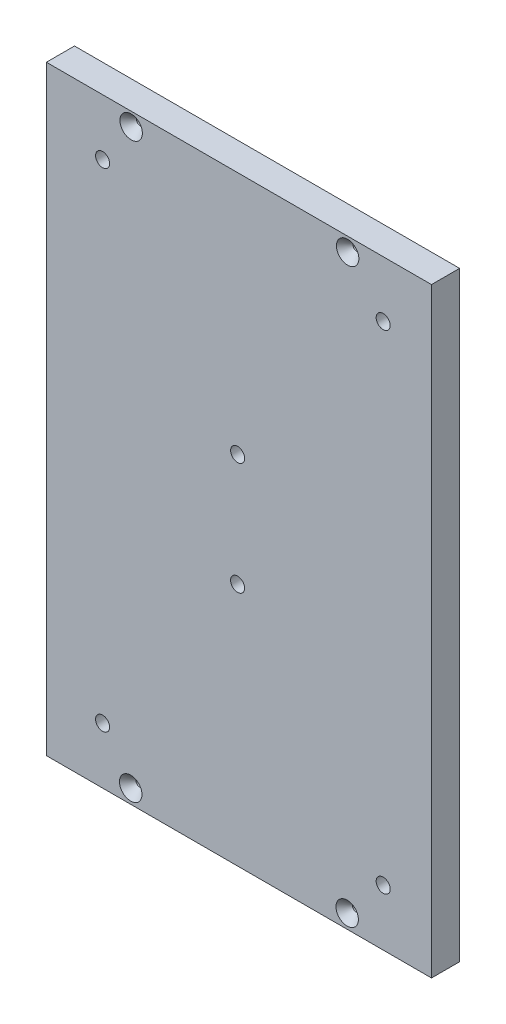
SolidWorks part; units mm, degrees
material "Beech"
ref_plane "Front Plane" through (0, 0, 0) normal (0, 0, 1) x (1, 0, 0)
ref_plane "Top Plane" through (0, 0, 0) normal (0, 1, 0) x (1, 0, 0)
ref_plane "Right Plane" through (0, 0, 0) normal (1, 0, 0) x (0, 0, -1)
sketch "Sketch1" plane through (0, 0, 0) normal (0, 0, 1) x (1, 0, 0)
  line L2 (125.2425, 0) -> (299.2638, 0)
  line L3 (125.2425, 0) -> (125.2425, 271.3655)
  line L4 (125.2425, 135.6828) -> (299.2638, 135.6828) construction
  line L5 (299.2638, 0) -> (299.2638, 271.3655)
  line L8 (125.2425, 271.3655) -> (299.2638, 271.3655)
  line L9 (299.2638, 0) -> (299.2638, 271.3655) construction
  point P15 (299.2638, 135.6828)
  point P16 (299.2638, 135.6828)
extrude "Boss-Extrude1" add sketch "Sketch1" along normal blind 12.7
hole_wizard "1/4 (0.25) Diameter Hole1" positions "Sketch2" profile "Sketch3" hole size "1/4" standard "ANSI Inch" end condition through all
sketch "Sketch2" plane through (0, 0, 0) normal (0, 0, -1) x (-1, 0, 0)
  point P0 (-277.4266, 245.9655)
  point P3 (-211.6533, 161.0828)
  point P6 (-150.6425, 245.9655)
  point P9 (-211.6533, 110.2828)
  point P12 (-277.4266, 25.4)
  point P15 (-150.6425, 25.4)
sketch "Sketch3" plane through (277.4266, 245.9655, 0) normal (1, 0, 0) x (0, 1, 0)
  line L0 (0, 0) -> (0, 12.7)
  line L1 (0, 12.7) -> (3.175, 12.7)
  line L2 (3.175, 12.7) -> (3.175, 0)
  line L5 (3.175, 0) -> (0, 0)
  line L11 (0, -6.35) -> (0, 107.95) construction
  dimension "Thru Hole Dia." = 6.35
  dimension "Thru Hole Depth" = 12.7
hole_wizard "Hole1" positions "Sketch4" profile "Sketch5" legacy
sketch "Sketch4" plane through (-504.9005, 135.8167, 12.7) normal (0, 0, 1) x (0, -1, 0)
  line L0 (129.4667, 804.1643) -> (129.4667, 630.143) construction
  line L5 (0.134, 804.1643) -> (0, 630.3901) construction
  point P10 (129.4667, 668.243)
  point P12 (129.4667, 766.0643)
  point P20 (-129.4082, 668.4425)
  point P21 (-129.2574, 766.2637)
sketch "Sketch5" plane through (261.3633, 265.0741, 12.7) normal (1, 0, 0) x (0, -1, 0)
  line L0 (0, 0) -> (0, 32.7039)
  line L1 (0, 32.7039) -> (1.5875, 31.75)
  line L2 (1.5875, 31.75) -> (1.5875, 4.0177)
  line L3 (1.5875, 4.0177) -> (5.08, 0)
  line L4 (5.08, 0) -> (0, 0)
  line L5 (0, -14.3089) -> (0, 102.4216) construction
  line L6 (0, 32.7039) -> (-1.5875, 31.75) construction
  line L7 (-1.5875, 4.0177) -> (-5.08, 0) construction
  dimension "Diameter" = 3.175
  dimension "Depth" = 31.75
  dimension "C-Sink Diameter" = 10.16
  dimension "C-Sink Angle" = 82
  dimension "Drill Angle" = 118
